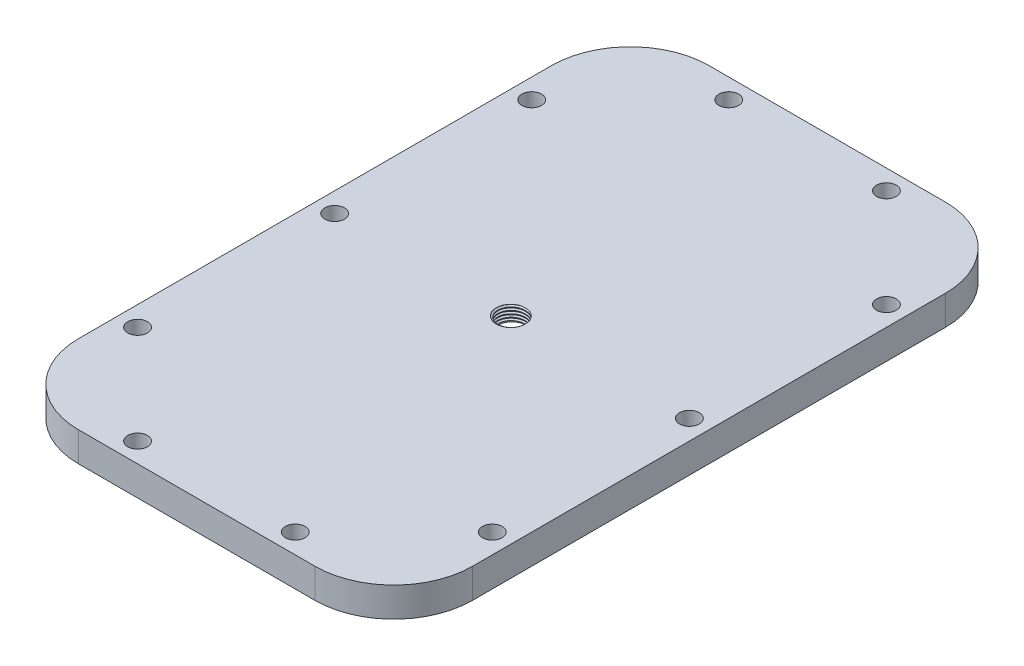
SolidWorks part; units mm, degrees
material "Plain Carbon Steel"
ref_plane "Front Plane" through (0, 0, 0) normal (0, 0, 1) x (1, 0, 0)
ref_plane "Top Plane" through (0, 0, 0) normal (0, 1, 0) x (1, 0, 0)
ref_plane "Right Plane" through (0, 0, 0) normal (1, 0, 0) x (0, 0, -1)
sketch "Sketch1" plane through (0, 0, 0) normal (0, 1, 0) x (1, 0, 0)
  line L0 (-100, -120) -> (-100, 120)
  line L1 (-60, -140) -> (60, -140)
  line L2 (-80, -120) -> (-80, 120)
  line L3 (-60, 140) -> (60, 140)
  line L4 (80, -120) -> (80, 120)
  line L5 (-80, -140) -> (80, 140) construction
  line L6 (-80, 140) -> (80, -140) construction
  line L7 (-60, 160) -> (60, 160)
  line L8 (100, -120) -> (100, 120)
  line L9 (-60, -160) -> (60, -160)
  arc A0 (60, -140) -> (80, -120) centre (60, -120) ccw
  arc A1 (-80, 120) -> (-60, 140) centre (-60, 120) cw
  arc A2 (-60, -140) -> (-80, -120) centre (-60, -120) cw
  arc A3 (60, 140) -> (80, 120) centre (60, 120) cw
  arc A4 (-100, 120) -> (-60, 160) centre (-60, 120) cw
  arc A5 (60, 160) -> (100, 120) centre (60, 120) cw
  arc A6 (60, -160) -> (100, -120) centre (60, -120) ccw
  arc A7 (-60, -160) -> (-100, -120) centre (-60, -120) cw
  point P0 (0, 0)
  dimension "D3" = 20
  dimension "D1" = 280
  dimension "D2" = 160
  dimension "D4" = 20
extrude "Boss-Extrude1" add sketch "Sketch1" along normal blind 15 contours L0 A4 L7 A5 L8 A6 L9 A7
sketch "Sketch2" plane through (0, 0, 0) normal (0, -1, 0) x (1, 0, 0)
  line L4 (80, -120) -> (80, 120)
  line L5 (60, 140) -> (-60, 140)
  line L6 (-80, 120) -> (-80, -120)
  line L7 (-60, -140) -> (60, -140)
  line L8 (80, -120) -> (80, 120)
  line L9 (60, 140) -> (-60, 140)
  line L10 (-80, 120) -> (-80, -120)
  line L11 (-60, -140) -> (60, -140)
  arc A4 (80, 120) -> (60, 140) centre (60, 120) ccw
  arc A5 (-60, 140) -> (-80, 120) centre (-60, 120) ccw
  arc A6 (-80, -120) -> (-60, -140) centre (-60, -120) ccw
  arc A7 (60, -140) -> (80, -120) centre (60, -120) ccw
  arc A8 (80, 120) -> (60, 140) centre (60, 120) ccw
  arc A9 (-60, 140) -> (-80, 120) centre (-60, 120) ccw
  arc A10 (-80, -120) -> (-60, -140) centre (-60, -120) ccw
  arc A11 (60, -140) -> (80, -120) centre (60, -120) ccw
  dimension "D1" = 0
extrude "Cut-Extrude1" cut sketch "Sketch2" against normal blind 7.5
sketch "Sketch3" plane through (0, 7.5, 0) normal (0, -1, 0) x (1, 0, 0)
  circle A0 centre (0, 0) radius 6.92
  dimension "D1" = 13.84
extrude "Cut-Extrude2" cut sketch "Sketch3" against normal up to surface (7.5 mm away) up to face at (0, 15, 0)
sketch "Sketch4" plane through (0, 0, 0) normal (0, -1, 0) x (1, 0, 0)
  line L20 (-90, 0) -> (90, 0) construction
  line L21 (0, 6.92) -> (0, -81.972) construction
  line L22 (-90, -120) -> (-90, 120) construction
  line L24 (-60, -150) -> (60, -150)
  line L25 (90, -120) -> (90, 120)
  line L26 (60, 150) -> (-60, 150)
  line L27 (-90, 120) -> (-90, -120)
  line L28 (-60, -150) -> (60, -150) construction
  line L29 (90, -120) -> (90, 120) construction
  line L30 (60, 150) -> (-60, 150) construction
  line L31 (-90, 120) -> (-90, -120) construction
  circle A16 centre (40, 150) radius 5
  circle A17 centre (90, 0) radius 5
  circle A18 centre (90, 100) radius 5
  circle A19 centre (90, -100) radius 5
  arc A20 (60, -150) -> (90, -120) centre (60, -120) ccw
  arc A21 (-90, -120) -> (-60, -150) centre (-60, -120) ccw
  arc A22 (90, 120) -> (60, 150) centre (60, 120) ccw
  arc A23 (-60, 150) -> (-90, 120) centre (-60, 120) ccw
  arc A24 (60, -150) -> (90, -120) centre (60, -120) ccw construction
  arc A25 (-90, -120) -> (-60, -150) centre (-60, -120) ccw construction
  arc A26 (90, 120) -> (60, 150) centre (60, 120) ccw construction
  arc A27 (-60, 150) -> (-90, 120) centre (-60, 120) ccw construction
  circle A28 centre (40, -150) radius 5
  circle A29 centre (0, 0) radius 6.92 construction
  arc A30 (-90, 120) -> (-60, 150) centre (-60, 120) cw construction
  arc A31 (-60, -150) -> (-90, -120) centre (-60, -120) cw construction
  circle A32 centre (-40, -150) radius 5
  circle A33 centre (-90, -100) radius 5
  circle A34 centre (-90, 100) radius 5
  circle A35 centre (-90, 0) radius 5
  circle A36 centre (-40, 150) radius 5
  point P16 (0, 0)
  dimension "D2" = 10
  dimension "D3" = 40
  dimension "D4" = 100
  dimension "D5" = 100
  dimension "D1" = 10
extrude "Cut-Extrude3" cut sketch "Sketch4" against normal up to surface (15 mm away) up to face at (0, 15, -6.92)
thread "Thread1" pitch 1.5 method cut profile "Thread Profile1" start angle 0, offset 0, length 0, pitch 1.5, diameter 13.84
ref_plane "Plane1" through (6.92, 7.5, 0) normal (0, 0, 1) x (1, 0, 0)
sketch "Thread Profile1" plane through (6.92, 7.5, 0) normal (0, 0, 1) x (1, 0, 0)
  line L0 (0, 0) -> (0, 1.5) construction
  line L1 (0, 0) -> (0.8119, 0.4687)
  line L2 (0.8119, 0.4687) -> (0.8119, 0.6562)
  line L3 (0.8119, 0.6562) -> (0, 1.125)
  line L4 (0.8119, 0.5625) -> (0, 0.5625) construction
  line L11 (0, 0) -> (0, 1.125)
  point P2 (0, 0)
  dimension "Pitch" = 1.5
  dimension "Profile_Angle" = 60
  dimension "Profile_Land" = 0.1875
  dimension "Profile_Height" = 0.8119
